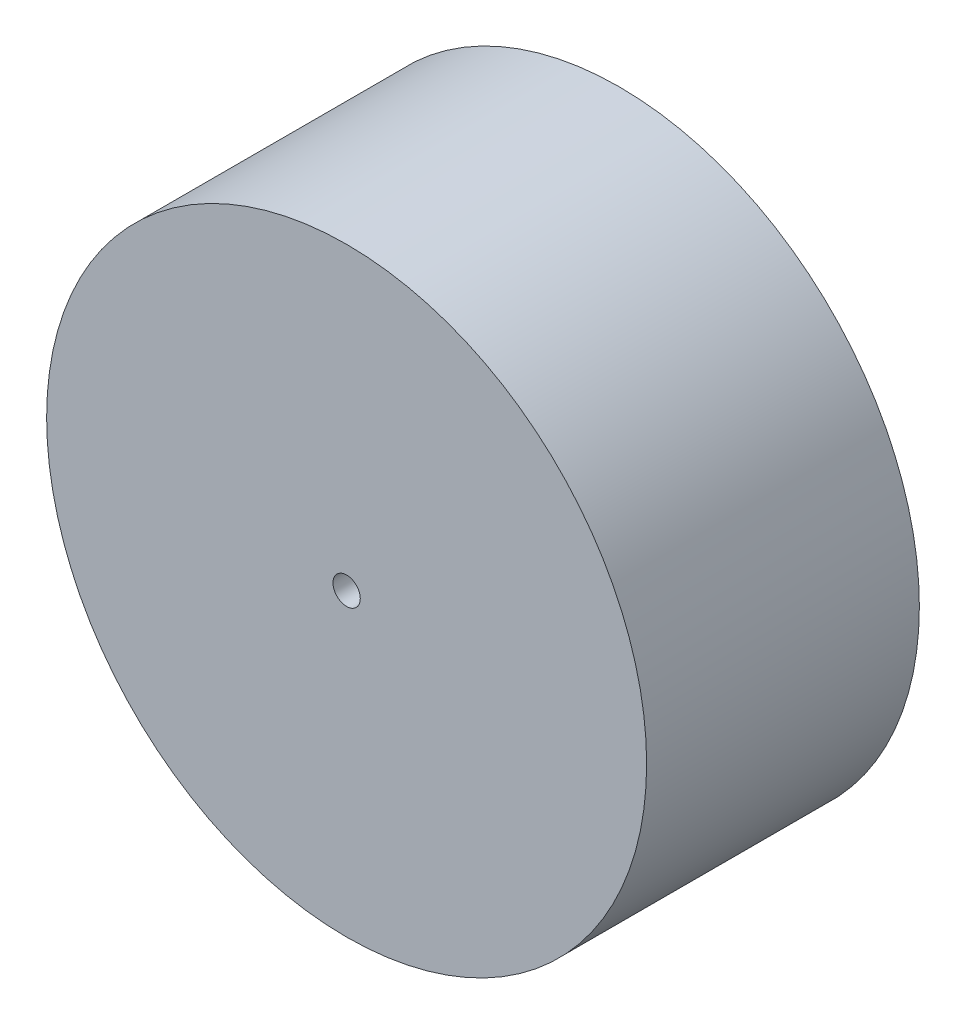
SolidWorks part; units mm, degrees
ref_plane "Front Plane" through (0, 0, 0) normal (0, 0, 1) x (1, 0, 0)
ref_plane "Top Plane" through (0, 0, 0) normal (0, 1, 0) x (1, 0, 0)
ref_plane "Right Plane" through (0, 0, 0) normal (1, 0, 0) x (0, 0, -1)
sketch "Sketch2" plane through (0, 0, 0) normal (0, 0, 1) x (1, 0, 0)
  circle A0 centre (0, 0) radius 139.7
  dimension "D1" = 279.4
extrude "Boss-Extrude1" add sketch "Sketch2" along normal blind 63.5 and the other way blind 63.5 contours A0
sketch "Sketch3" plane through (0, 0, 63.5) normal (0, 0, 1) x (1, 0, 0)
  circle A0 centre (0, 0) radius 6.35
  dimension "D1" = 12.7
extrude "Cut-Extrude1" cut sketch "Sketch3" against normal through all
equation "\"tire_thickness\"=0.5"
equation "\"wheel_thickness\"=5"
equation "\"wheel_dia\"=12"
equation "\"D1@Sketch2\"=\"wheel_dia\"-(\"tire_thickness\"*2)"
equation "\"D1@Boss-Extrude1\"=\"wheel_thickness\" /2"
equation "\"shaft_dia\"= .5"
equation "\"D1@Sketch3\"=\"shaft_dia\""
equation "\"D2@Boss-Extrude1\"=\"wheel_thickness\" /2"
